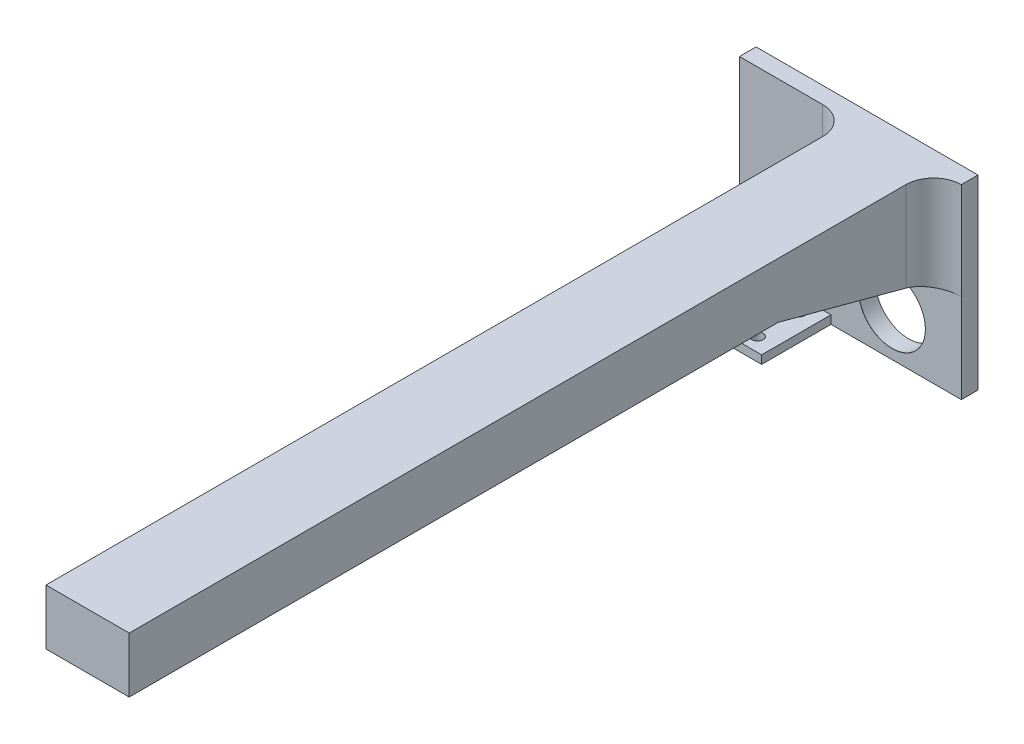
SolidWorks part; units mm, degrees
ref_plane "Front Plane" through (0, 0, 0) normal (0, 0, 1) x (1, 0, 0)
ref_plane "Top Plane" through (0, 0, 0) normal (0, 1, 0) x (1, 0, 0)
ref_plane "Right Plane" through (0, 0, 0) normal (1, 0, 0) x (0, 0, -1)
sketch "Sketch1" plane through (0, 0, 0) normal (0, 0, 1) x (1, 0, 0)
  line L1 (-40, 36.785) -> (40, 36.785)
  line L2 (-40, 36.785) -> (-40, -36.785)
  line L3 (-40, -36.785) -> (40, -36.785)
  line L4 (40, 36.785) -> (40, -36.785)
  line L5 (-40, 36.785) -> (40, -36.785) construction
  line L6 (-40, -36.785) -> (40, 36.785) construction
  point P0 (0, 0)
  dimension "D1" = 80
  dimension "D2" = 73.57
extrude "Boss-Extrude1" add sketch "Sketch1" along normal mid plane 6
sketch "Sketch2" plane through (0, 0, 3) normal (0, 0, 1) x (1, 0, 0)
  line L0 (-40, 36.785) -> (-40, -36.785) construction
  line L1 (-40, -30.355) -> (-7, -30.355)
  line L2 (-40, -30.355) -> (-40, -27.355)
  line L3 (-40, -27.355) -> (-7, -27.355)
  line L4 (-7, -30.355) -> (-7, -27.355)
  line L5 (-40, -36.785) -> (40, -36.785) construction
  dimension "D1" = 3
  dimension "D2" = 33
  dimension "D3" = 6.43
extrude "Boss-Extrude2" add sketch "Sketch2" along normal blind 25
hole_wizard "Ø4.0 (4) Diameter Hole1" positions "Sketch3" profile "Sketch4" hole size "Ø4.0" standard "ANSI Metric"
sketch "Sketch3" plane through (0, -27.355, 0) normal (0, 1, 0) x (1, 0, 0)
  line L0 (-7, -28) -> (-7, -3) construction
  line L1 (-7, -28) -> (-40, -28) construction
  line L2 (-40, -28) -> (-40, -3) construction
  point P0 (-33.5, -8)
  point P2 (-13.5, -8)
  point P4 (-13.5, -23)
  point P6 (-33.5, -23)
  dimension "D1" = 20
  dimension "D2" = 15
  dimension "D3" = 6.5
  dimension "D4" = 5
  dimension "D5" = 6.5
sketch "Sketch4" plane through (-33.5, -27.355, 8) normal (1, 0, 0) x (0, 0, 1)
  line L0 (0, 0) -> (0, 9.2017)
  line L1 (0, 9.2017) -> (2, 8)
  line L2 (2, 8) -> (2, 0.025)
  line L3 (2, 0.025) -> (2.025, 0)
  line L5 (2.025, 0) -> (0, 0)
  line L6 (-2, 0.025) -> (-2.025, 0) construction
  line L10 (0, 9.2017) -> (-2, 8) construction
  line L11 (0, -6.35) -> (0, 107.95) construction
  dimension "Hole Dia." = 4
  dimension "Hole Depth" = 8
  dimension "Near C'Sink Dia." = 4.05
  dimension "Near C'Sink Angle" = 90
  dimension "Drill Angle" = 118
hole_wizard "Ø24.0 (24) Diameter Hole1" positions "Sketch7" profile "Sketch8" hole size "Ø24.0" standard "ANSI Metric"
sketch "Sketch7" plane through (0, 0, 3) normal (0, 0, 1) x (1, 0, 0)
  line L0 (-40, -36.785) -> (40, -36.785) construction
  line L1 (40, -36.785) -> (40, 36.785) construction
  point P0 (15, -14.855)
  dimension "D1" = 21.93
  dimension "D2" = 25
sketch "Sketch8" plane through (15, -14.855, 3) normal (1, 0, 0) x (0, -1, 0)
  line L0 (0, 0) -> (0, 15.2103)
  line L1 (0, 15.2103) -> (12, 8)
  line L2 (12, 8) -> (12, 0.025)
  line L3 (12, 0.025) -> (12.025, 0)
  line L5 (12.025, 0) -> (0, 0)
  line L6 (-12, 0.025) -> (-12.025, 0) construction
  line L10 (0, 15.2103) -> (-12, 8) construction
  line L11 (0, -6.35) -> (0, 107.95) construction
  dimension "Hole Dia." = 24
  dimension "Hole Depth" = 8
  dimension "Near C'Sink Dia." = 24.05
  dimension "Near C'Sink Angle" = 90
  dimension "Drill Angle" = 118
sketch "Sketch9" plane through (0, 0, 3) normal (0, 0, 1) x (1, 0, 0)
  line L0 (40, -36.785) -> (40, 36.785) construction
  line L1 (-40, 36.785) -> (40, 36.785)
  line L2 (-40, 36.785) -> (-40, 21.785)
  line L3 (-40, 21.785) -> (40, 21.785)
  line L4 (40, 36.785) -> (40, 21.785)
  dimension "D1" = 80
  dimension "D2" = 15
extrude "Cut-Extrude1" [suppressed] cut sketch "Sketch9" against normal blind 15
sketch "Sketch10" plane through (0, 0, -3) normal (0, 0, -1) x (-1, 0, 0)
  line L1 (-40, -11.785) -> (-90, -11.785)
  line L2 (-40, -11.785) -> (-40, -36.785)
  line L3 (-40, -36.785) -> (-90, -36.785)
  line L4 (-90, -11.785) -> (-90, -36.785)
  dimension "D1" = 50
  dimension "D2" = 25
extrude "Boss-Extrude4" [suppressed] add sketch "Sketch10" against normal blind 30
chamfer "Chamfer2" [suppressed] distance 25 angle 45
sketch "Sketch11" plane through (-40, 0, 0) normal (-1, 0, 0) x (0, 0, 1)
  line L0 (3, -30.355) -> (3, -36.785) construction
  line L1 (-3, -36.785) -> (3, -36.785)
  line L2 (-3, -36.785) -> (-3, -30.355)
  line L3 (-3, -30.355) -> (3, -30.355)
  line L4 (3, -36.785) -> (3, -30.355)
  dimension "D1" = 6.43
extrude "Cut-Extrude2" cut sketch "Sketch11" against normal through all
sketch "Sketch12" plane through (0, 0, 3) normal (0, 0, 1) x (1, 0, 0)
  line L0 (40, 36.785) -> (-40, 36.785) construction
  line L1 (0, 36.785) -> (30, 36.785)
  line L2 (0, 36.785) -> (0, 16.785)
  line L3 (0, 16.785) -> (30, 16.785)
  line L4 (30, 36.785) -> (30, 16.785)
  line L5 (40, -30.355) -> (40, 36.785) construction
  dimension "D1" = 20
  dimension "D2" = 30
  dimension "D3" = 10
extrude "Boss-Extrude5" add sketch "Sketch12" along normal blind 290
chamfer "Chamfer3" distance 15 angle 75 1 edges at (15, 16.785, 3) first distance on face at (27.025, -14.855, 3)
fillet "Fillet1" radius 10 2 edges at (0, 19.285, 3) (30, 19.285, 3)
